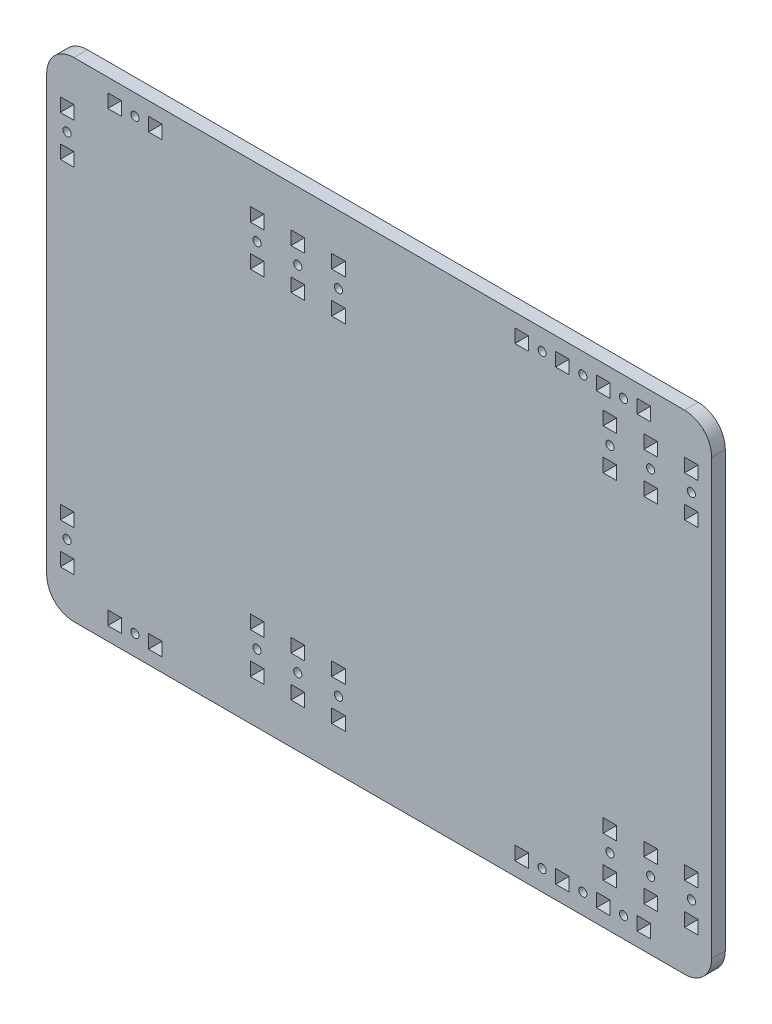
SolidWorks part; units mm, degrees
ref_plane "Front Plane" through (0, 0, 0) normal (0, 0, 1) x (1, 0, 0)
ref_plane "Top Plane" through (0, 0, 0) normal (0, 1, 0) x (1, 0, 0)
ref_plane "Right Plane" through (0, 0, 0) normal (1, 0, 0) x (0, 0, -1)
sketch "Sketch1" plane through (0, 0, 0) normal (0, 0, 1) x (1, 0, 0)
  line L0 (0, 0) -> (264.3375, 0) construction
  line L1 (-91.3244, 90) -> (153.676, 90)
  line L5 (23.6756, 97.7888) -> (23.6756, -107.1048) construction
  line L6 (-92.4996, 82.5) -> (92.5, 82.5) construction
  line L7 (92.5, -82.5) -> (-92.4996, -82.5) construction
  line L8 (-91.3244, 90) -> (-91.3244, -90)
  line L51 (-83.8244, 77.0051) -> (-83.8244, -67.4641) construction
  line L105 (-91.3244, -90) -> (153.676, -90)
  line L122 (153.676, 90) -> (153.676, -90)
  line L124 (-83.8244, 65) -> (153.676, 65) construction
  line L125 (-83.8244, -65) -> (153.676, -65) construction
  point P26 (127.5, -49.75)
  line B0 (-63.8248, 82.5) -> (-53.8248, 82.5) construction
  line B1 (-63.8248, 85) -> (-68.8248, 85)
  line B2 (-63.8248, 85) -> (-63.8248, 80)
  line B3 (-63.8248, 80) -> (-68.8248, 80)
  line B4 (-68.8248, 85) -> (-68.8248, 80)
  line B5 (-53.8248, 85) -> (-48.8248, 85)
  line B6 (-53.8248, 85) -> (-53.8248, 80)
  line B7 (-53.8248, 80) -> (-48.8248, 80)
  line B8 (-48.8248, 85) -> (-48.8248, 80)
  line B9 (-58.8248, 82.5) -> (-58.8248, 89.4724) construction
  circle B10 centre (-58.8248, 82.5) radius 1.5
  line B11 (111.176, 82.5) -> (101.176, 82.5) construction
  line B12 (111.176, 85) -> (116.176, 85)
  line B13 (111.176, 85) -> (111.176, 80)
  line B14 (111.176, 80) -> (116.176, 80)
  line B15 (116.176, 85) -> (116.176, 80)
  line B16 (101.176, 85) -> (96.176, 85)
  line B17 (101.176, 85) -> (101.176, 80)
  line B18 (101.176, 80) -> (96.176, 80)
  line B19 (96.176, 85) -> (96.176, 80)
  line B20 (106.176, 82.5) -> (106.176, 89.4724) construction
  circle B21 centre (106.176, 82.5) radius 1.5
  line B22 (111.176, -82.5) -> (101.176, -82.5) construction
  line B23 (111.176, -85) -> (116.176, -85)
  line B24 (111.176, -85) -> (111.176, -80)
  line B25 (111.176, -80) -> (116.176, -80)
  line B26 (116.176, -85) -> (116.176, -80)
  line B27 (101.176, -85) -> (96.176, -85)
  line B28 (101.176, -85) -> (101.176, -80)
  line B29 (101.176, -80) -> (96.176, -80)
  line B30 (96.176, -85) -> (96.176, -80)
  line B31 (106.176, -82.5) -> (106.176, -89.4724) construction
  circle B32 centre (106.176, -82.5) radius 1.5
  line B33 (-63.8248, -82.5) -> (-53.8248, -82.5) construction
  line B34 (-63.8248, -85) -> (-68.8248, -85)
  line B35 (-63.8248, -85) -> (-63.8248, -80)
  line B36 (-63.8248, -80) -> (-68.8248, -80)
  line B37 (-68.8248, -85) -> (-68.8248, -80)
  line B38 (-53.8248, -85) -> (-48.8248, -85)
  line B39 (-53.8248, -85) -> (-53.8248, -80)
  line B40 (-53.8248, -80) -> (-48.8248, -80)
  line B41 (-48.8248, -85) -> (-48.8248, -80)
  line B42 (-58.8248, -82.5) -> (-58.8248, -89.4724) construction
  circle B43 centre (-58.8248, -82.5) radius 1.5
  line B44 (96.176, 82.5) -> (86.176, 82.5) construction
  line B45 (96.176, 85) -> (101.176, 85)
  line B46 (96.176, 85) -> (96.176, 80)
  line B47 (96.176, 80) -> (101.176, 80)
  line B48 (101.176, 85) -> (101.176, 80)
  line B49 (86.176, 85) -> (81.176, 85)
  line B50 (86.176, 85) -> (86.176, 80)
  line B51 (86.176, 80) -> (81.176, 80)
  line B52 (81.176, 85) -> (81.176, 80)
  line B53 (91.176, 82.5) -> (91.176, 89.4724) construction
  circle B54 centre (91.176, 82.5) radius 1.5
  line B55 (126.176, 82.5) -> (116.176, 82.5) construction
  line B56 (126.176, 85) -> (131.176, 85)
  line B57 (126.176, 85) -> (126.176, 80)
  line B58 (126.176, 80) -> (131.176, 80)
  line B59 (131.176, 85) -> (131.176, 80)
  line B60 (116.176, 85) -> (111.176, 85)
  line B61 (116.176, 85) -> (116.176, 80)
  line B62 (116.176, 80) -> (111.176, 80)
  line B63 (111.176, 85) -> (111.176, 80)
  line B64 (121.176, 82.5) -> (121.176, 89.4724) construction
  circle B65 centre (121.176, 82.5) radius 1.5
  line B66 (96.176, -82.5) -> (86.176, -82.5) construction
  line B67 (96.176, -85) -> (101.176, -85)
  line B68 (96.176, -85) -> (96.176, -80)
  line B69 (96.176, -80) -> (101.176, -80)
  line B70 (101.176, -85) -> (101.176, -80)
  line B71 (86.176, -85) -> (81.176, -85)
  line B72 (86.176, -85) -> (86.176, -80)
  line B73 (86.176, -80) -> (81.176, -80)
  line B74 (81.176, -85) -> (81.176, -80)
  line B75 (91.176, -82.5) -> (91.176, -89.4724) construction
  circle B76 centre (91.176, -82.5) radius 1.5
  line B77 (126.176, -82.5) -> (116.176, -82.5) construction
  line B78 (126.176, -85) -> (131.176, -85)
  line B79 (126.176, -85) -> (126.176, -80)
  line B80 (126.176, -80) -> (131.176, -80)
  line B81 (131.176, -85) -> (131.176, -80)
  line B82 (116.176, -85) -> (111.176, -85)
  line B83 (116.176, -85) -> (116.176, -80)
  line B84 (116.176, -80) -> (111.176, -80)
  line B85 (111.176, -85) -> (111.176, -80)
  line B86 (121.176, -82.5) -> (121.176, -89.4724) construction
  circle B87 centre (121.176, -82.5) radius 1.5
  line B88 (-83.8244, 70) -> (-83.8244, 60) construction
  line B89 (-86.3244, 70) -> (-86.3244, 75)
  line B90 (-86.3244, 70) -> (-81.3244, 70)
  line B91 (-81.3244, 70) -> (-81.3244, 75)
  line B92 (-86.3244, 75) -> (-81.3244, 75)
  line B93 (-86.3244, 60) -> (-86.3244, 55)
  line B94 (-86.3244, 60) -> (-81.3244, 60)
  line B95 (-81.3244, 60) -> (-81.3244, 55)
  line B96 (-86.3244, 55) -> (-81.3244, 55)
  line B97 (-83.8244, 65) -> (-90.7968, 65) construction
  circle B98 centre (-83.8244, 65) radius 1.5
  line B99 (-83.8244, -60) -> (-83.8244, -70) construction
  line B100 (-86.3244, -60) -> (-86.3244, -55)
  line B101 (-86.3244, -60) -> (-81.3244, -60)
  line B102 (-81.3244, -60) -> (-81.3244, -55)
  line B103 (-86.3244, -55) -> (-81.3244, -55)
  line B104 (-86.3244, -70) -> (-86.3244, -75)
  line B105 (-86.3244, -70) -> (-81.3244, -70)
  line B106 (-81.3244, -70) -> (-81.3244, -75)
  line B107 (-86.3244, -75) -> (-81.3244, -75)
  line B108 (-83.8244, -65) -> (-90.7968, -65) construction
  circle B109 centre (-83.8244, -65) radius 1.5
  line B110 (146.176, 70) -> (146.176, 60) construction
  line B111 (143.676, 70) -> (143.676, 75)
  line B112 (143.676, 70) -> (148.676, 70)
  line B113 (148.676, 70) -> (148.676, 75)
  line B114 (143.676, 75) -> (148.676, 75)
  line B115 (143.676, 60) -> (143.676, 55)
  line B116 (143.676, 60) -> (148.676, 60)
  line B117 (148.676, 60) -> (148.676, 55)
  line B118 (143.676, 55) -> (148.676, 55)
  line B119 (146.176, 65) -> (139.2036, 65) construction
  circle B120 centre (146.176, 65) radius 1.5
  line B121 (146.176, -60) -> (146.176, -70) construction
  line B122 (143.676, -60) -> (143.676, -55)
  line B123 (143.676, -60) -> (148.676, -60)
  line B124 (148.676, -60) -> (148.676, -55)
  line B125 (143.676, -55) -> (148.676, -55)
  line B126 (143.676, -70) -> (143.676, -75)
  line B127 (143.676, -70) -> (148.676, -70)
  line B128 (148.676, -70) -> (148.676, -75)
  line B129 (143.676, -75) -> (148.676, -75)
  line B130 (146.176, -65) -> (139.2036, -65) construction
  circle B131 centre (146.176, -65) radius 1.5
  line B132 (131.176, -60) -> (131.176, -70) construction
  line B133 (128.676, -60) -> (128.676, -55)
  line B134 (128.676, -60) -> (133.676, -60)
  line B135 (133.676, -60) -> (133.676, -55)
  line B136 (128.676, -55) -> (133.676, -55)
  line B137 (128.676, -70) -> (128.676, -75)
  line B138 (128.676, -70) -> (133.676, -70)
  line B139 (133.676, -70) -> (133.676, -75)
  line B140 (128.676, -75) -> (133.676, -75)
  line B141 (131.176, -65) -> (124.2036, -65) construction
  circle B142 centre (131.176, -65) radius 1.5
  line B143 (116.176, -60) -> (116.176, -70) construction
  line B144 (113.676, -60) -> (113.676, -55)
  line B145 (113.676, -60) -> (118.676, -60)
  line B146 (118.676, -60) -> (118.676, -55)
  line B147 (113.676, -55) -> (118.676, -55)
  line B148 (113.676, -70) -> (113.676, -75)
  line B149 (113.676, -70) -> (118.676, -70)
  line B150 (118.676, -70) -> (118.676, -75)
  line B151 (113.676, -75) -> (118.676, -75)
  line B152 (116.176, -65) -> (109.2036, -65) construction
  circle B153 centre (116.176, -65) radius 1.5
  line B154 (131.176, 70) -> (131.176, 60) construction
  line B155 (128.676, 70) -> (128.676, 75)
  line B156 (128.676, 70) -> (133.676, 70)
  line B157 (133.676, 70) -> (133.676, 75)
  line B158 (128.676, 75) -> (133.676, 75)
  line B159 (128.676, 60) -> (128.676, 55)
  line B160 (128.676, 60) -> (133.676, 60)
  line B161 (133.676, 60) -> (133.676, 55)
  line B162 (128.676, 55) -> (133.676, 55)
  line B163 (131.176, 65) -> (124.2036, 65) construction
  circle B164 centre (131.176, 65) radius 1.5
  line B165 (116.176, 70) -> (116.176, 60) construction
  line B166 (113.676, 70) -> (113.676, 75)
  line B167 (113.676, 70) -> (118.676, 70)
  line B168 (118.676, 70) -> (118.676, 75)
  line B169 (113.676, 75) -> (118.676, 75)
  line B170 (113.676, 60) -> (113.676, 55)
  line B171 (113.676, 60) -> (118.676, 60)
  line B172 (118.676, 60) -> (118.676, 55)
  line B173 (113.676, 55) -> (118.676, 55)
  line B174 (116.176, 65) -> (109.2036, 65) construction
  circle B175 centre (116.176, 65) radius 1.5
  line B176 (16.1756, -60) -> (16.1756, -70) construction
  line B177 (13.6756, -60) -> (13.6756, -55)
  line B178 (13.6756, -60) -> (18.6756, -60)
  line B179 (18.6756, -60) -> (18.6756, -55)
  line B180 (13.6756, -55) -> (18.6756, -55)
  line B181 (13.6756, -70) -> (13.6756, -75)
  line B182 (13.6756, -70) -> (18.6756, -70)
  line B183 (18.6756, -70) -> (18.6756, -75)
  line B184 (13.6756, -75) -> (18.6756, -75)
  line B185 (16.1756, -65) -> (9.2032, -65) construction
  circle B186 centre (16.1756, -65) radius 1.5
  line B187 (1.1756, -60) -> (1.1756, -70) construction
  line B188 (-1.3244, -60) -> (-1.3244, -55)
  line B189 (-1.3244, -60) -> (3.6756, -60)
  line B190 (3.6756, -60) -> (3.6756, -55)
  line B191 (-1.3244, -55) -> (3.6756, -55)
  line B192 (-1.3244, -70) -> (-1.3244, -75)
  line B193 (-1.3244, -70) -> (3.6756, -70)
  line B194 (3.6756, -70) -> (3.6756, -75)
  line B195 (-1.3244, -75) -> (3.6756, -75)
  line B196 (1.1756, -65) -> (-5.7968, -65) construction
  circle B197 centre (1.1756, -65) radius 1.5
  line B198 (-13.8244, -60) -> (-13.8244, -70) construction
  line B199 (-16.3244, -60) -> (-16.3244, -55)
  line B200 (-16.3244, -60) -> (-11.3244, -60)
  line B201 (-11.3244, -60) -> (-11.3244, -55)
  line B202 (-16.3244, -55) -> (-11.3244, -55)
  line B203 (-16.3244, -70) -> (-16.3244, -75)
  line B204 (-16.3244, -70) -> (-11.3244, -70)
  line B205 (-11.3244, -70) -> (-11.3244, -75)
  line B206 (-16.3244, -75) -> (-11.3244, -75)
  line B207 (-13.8244, -65) -> (-20.7968, -65) construction
  circle B208 centre (-13.8244, -65) radius 1.5
  line B209 (16.1756, 60) -> (16.1756, 70) construction
  line B210 (13.6756, 60) -> (13.6756, 55)
  line B211 (13.6756, 60) -> (18.6756, 60)
  line B212 (18.6756, 60) -> (18.6756, 55)
  line B213 (13.6756, 55) -> (18.6756, 55)
  line B214 (13.6756, 70) -> (13.6756, 75)
  line B215 (13.6756, 70) -> (18.6756, 70)
  line B216 (18.6756, 70) -> (18.6756, 75)
  line B217 (13.6756, 75) -> (18.6756, 75)
  line B218 (16.1756, 65) -> (9.2032, 65) construction
  circle B219 centre (16.1756, 65) radius 1.5
  line B220 (1.1756, 60) -> (1.1756, 70) construction
  line B221 (-1.3244, 60) -> (-1.3244, 55)
  line B222 (-1.3244, 60) -> (3.6756, 60)
  line B223 (3.6756, 60) -> (3.6756, 55)
  line B224 (-1.3244, 55) -> (3.6756, 55)
  line B225 (-1.3244, 70) -> (-1.3244, 75)
  line B226 (-1.3244, 70) -> (3.6756, 70)
  line B227 (3.6756, 70) -> (3.6756, 75)
  line B228 (-1.3244, 75) -> (3.6756, 75)
  line B229 (1.1756, 65) -> (-5.7968, 65) construction
  circle B230 centre (1.1756, 65) radius 1.5
  line B231 (-13.8244, 60) -> (-13.8244, 70) construction
  line B232 (-16.3244, 60) -> (-16.3244, 55)
  line B233 (-16.3244, 60) -> (-11.3244, 60)
  line B234 (-11.3244, 60) -> (-11.3244, 55)
  line B235 (-16.3244, 55) -> (-11.3244, 55)
  line B236 (-16.3244, 70) -> (-16.3244, 75)
  line B237 (-16.3244, 70) -> (-11.3244, 70)
  line B238 (-11.3244, 70) -> (-11.3244, 75)
  line B239 (-16.3244, 75) -> (-11.3244, 75)
  line B240 (-13.8244, 65) -> (-20.7968, 65) construction
  circle B241 centre (-13.8244, 65) radius 1.5
  dimension "D1" = 165
  dimension "D2" = 7.5
  dimension "D3" = 15
  dimension "D4" = 32.4996
  dimension "D5" = 32.5
  dimension "D6" = 7.5
  dimension "D7" = 15
  dimension "D9" = 115
  dimension "D10" = 23.6756
  dimension "D13" = 7.5
  dimension "D14" = 25
  dimension "D18" = 7.5
  dimension "D19" = 15
  dimension "D20" = 15
sketch_block_instance "Trou M3 plots 5mm-1"
sketch_block "Trou M3 plots 5mm" parameters "D2"=3, "D1"=5, "D3"=5, "D4"=10
sketch_block_instance "Trou M3 plots 5mm-3"
sketch_block_instance "Trou M3 plots 5mm-4"
sketch_block_instance "Trou M3 plots 5mm-5"
sketch_block_instance "Trou M3 plots 5mm-15"
sketch_block_instance "Trou M3 plots 5mm-16"
sketch_block_instance "Trou M3 plots 5mm-18"
sketch_block_instance "Trou M3 plots 5mm-19"
sketch_block_instance "Trou M3 plots 5mm-20"
sketch_block_instance "Trou M3 plots 5mm-21"
sketch_block_instance "Trou M3 plots 5mm-22"
sketch_block_instance "Trou M3 plots 5mm-23"
sketch_block_instance "Trou M3 plots 5mm-24"
sketch_block_instance "Trou M3 plots 5mm-25"
sketch_block_instance "Trou M3 plots 5mm-26"
sketch_block_instance "Trou M3 plots 5mm-27"
sketch_block_instance "Trou M3 plots 5mm-28"
sketch_block_instance "Trou M3 plots 5mm-29"
sketch_block_instance "Trou M3 plots 5mm-30"
sketch_block_instance "Trou M3 plots 5mm-34"
sketch_block_instance "Trou M3 plots 5mm-35"
sketch_block_instance "Trou M3 plots 5mm-36"
extrude "Boss-Extrude1" add sketch "Sketch1" along normal blind 5 contours L122 L1 L8 L105 B87 B81 B78 B79 B80 B76 B56 B59 B58 B57 B54 B52 B49 B50 B51 region at (30.7392, 0, 0)
fillet "Fillet1" radius 10 4 edges at (153.676, 90, 2.5) (153.676, -90, 2.5) (-91.3244, -90, 2.5) (-91.3244, 90, 2.5)
